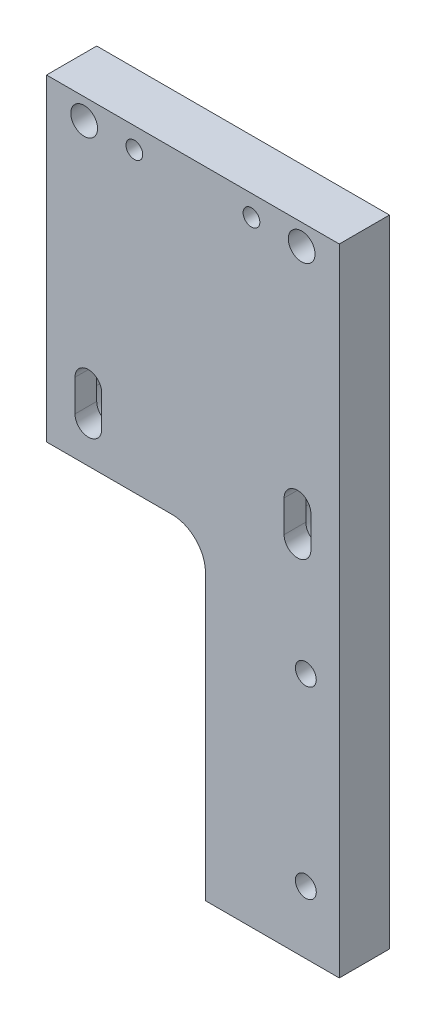
SolidWorks part; units mm, degrees
ref_plane "Front Plane" through (0, 0, 0) normal (0, 0, 1) x (1, 0, 0)
ref_plane "Top Plane" through (0, 0, 0) normal (0, 1, 0) x (1, 0, 0)
ref_plane "Right Plane" through (0, 0, 0) normal (1, 0, 0) x (0, 0, -1)
sketch "Sketch1" plane through (0, 0, 0) normal (0, 1, 0) x (1, 0, 0)
  line L1 (0, 0) -> (35, 0)
  line L2 (0, 0) -> (0, 6)
  line L3 (0, 6) -> (35, 6)
  line L4 (35, 0) -> (35, 6)
  dimension "D1" = 6
  dimension "D2" = 35
extrude "Boss-Extrude1" add sketch "Sketch1" along normal blind 76
sketch "Sketch2" plane through (0, 0, 0) normal (0, 0, 1) x (1, 0, 0)
  line L0 (17.5, 76) -> (17.5, 0) construction
  line L1 (0, 76) -> (35, 76) construction
  line L2 (0, 0) -> (35, 0) construction
  circle A0 centre (4.5, 73.5) radius 1.6
  circle A1 centre (30.5, 73.5) radius 1.6
  dimension "D3" = 3.2
  dimension "D1" = 2.5
  dimension "D2" = 2.5
  dimension "D4" = 13
  dimension "D5" = 13
extrude "Cut-Extrude1" cut sketch "Sketch2" against normal through all
sketch "Sketch3" plane through (0, 0, 0) normal (0, 0, 1) x (1, 0, 0)
  line L0 (17.5, 76) -> (17.5, 0) construction
  line L1 (0, 76) -> (35, 76) construction
  line L2 (0, 0) -> (35, 0) construction
  circle A0 centre (10.5, 73.5) radius 1
  circle A1 centre (24.5, 73.5) radius 1
  dimension "D5" = 2
  dimension "D1" = 7
  dimension "D2" = 7
  dimension "D3" = 2.5
  dimension "D4" = 2.5
extrude "Cut-Extrude2" cut sketch "Sketch3" against normal blind 4
hole_wizard "CBORE SLOT for M3 Hex Socket Head Cap Screw1" positions "Sketch4" profile "Sketch6" size "M3" standard "DIN" slot yes end condition through all
sketch "Sketch4" plane through (0, 0, -6) normal (0, 0, -1) x (-1, 0, 0)
  line L0 (-30, 41) -> (-30, 48) construction
  line L1 (-35, 76) -> (-35, 0) construction
  line L3 (0, 76) -> (0, 0) construction
  line L4 (-35, 76) -> (0, 76) construction
  point P0 (-30, 44.5)
  point P4 (-5, 44.5)
  dimension "D1" = 7
  dimension "D2" = 5
  dimension "D3" = 31.5
  dimension "D4" = 31.5
  dimension "D5" = 5
sketch "Sketch6" plane through (30, 44.5, -6) normal (1, 0, 0) x (0, 1, 0)
  line L0 (0, 0) -> (0, 6)
  line L1 (0, 6) -> (1.6, 6)
  line L3 (1.6, 6) -> (1.6, 3.4)
  line L4 (1.6, 3.4) -> (3.25, 3.4)
  line L5 (3.25, 3.4) -> (3.25, 0)
  line L7 (3.25, 0) -> (0, 0)
  line L11 (0, -6.35) -> (0, 107.95) construction
  dimension "Thru Hole Dia." = 3.2
  dimension "Thru Hole Depth" = 6
  dimension "C'Bore Dia." = 6.5
  dimension "C'Bore Depth" = 3.4
ref_plane "Plane1" through (17.5, 0, 0) normal (1, 0, 0) x (0, 0, -1)
sketch "Sketch7" plane through (0, 0, -6) normal (0, 0, -1) x (-1, 0, 0)
  line L0 (0, 0) -> (-19, 0)
  line L6 (-35, 0) -> (0, 0) construction
  line L8 (0, 76) -> (0, 0) construction
  line L9 (0, 38) -> (0, 0)
  line L10 (-19, 0) -> (-19, 34)
  line L11 (-15, 38) -> (0, 38)
  arc A0 (-19, 34) -> (-15, 38) centre (-15, 34) cw
  dimension "D3" = 4
  dimension "D1" = 38
  dimension "D2" = 16
extrude "Cut-Extrude3" cut sketch "Sketch7" against normal through all
sketch "Sketch8" plane through (0, 0, -6) normal (0, 0, -1) x (-1, 0, 0)
  line L0 (-35, 18.5) -> (-19, 18.5) construction
  line L1 (-35, 76) -> (-35, 0) construction
  line L3 (-35, 0) -> (-19, 0) construction
  line L4 (-19, 34) -> (-19, 0) construction
  circle A0 centre (-31, 7.5) radius 1.25
  circle A2 centre (-31, 29.5) radius 1.25
  point P4 (-19, 18.5)
  point P12 (-9.75, 18.5)
  dimension "D3" = 2.5
  dimension "D1" = 18.5
  dimension "D4" = 11
  dimension "D5" = 4
extrude "Cut-Extrude4" cut sketch "Sketch8" against normal through all
